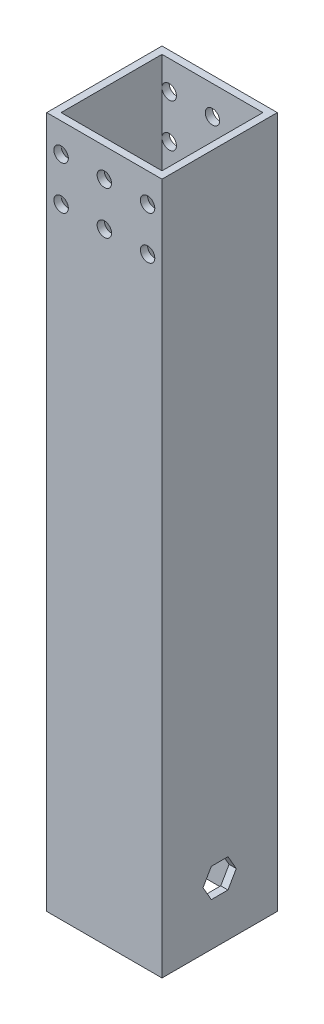
SolidWorks part; units mm, degrees
ref_plane "Front Plane" through (0, 0, 0) normal (0, 0, 1) x (1, 0, 0)
ref_plane "Top Plane" through (0, 0, 0) normal (0, 1, 0) x (1, 0, 0)
ref_plane "Right Plane" through (0, 0, 0) normal (1, 0, 0) x (0, 0, -1)
sketch "Sketch1" plane through (0, 0, 0) normal (0, 1, 0) x (1, 0, 0)
  line L1 (-25.4, -25.4) -> (25.4, -25.4)
  line L2 (-25.4, -25.4) -> (-25.4, 25.4)
  line L3 (-25.4, 25.4) -> (25.4, 25.4)
  line L4 (25.4, -25.4) -> (25.4, 25.4)
  line L5 (-25.4, -25.4) -> (25.4, 25.4) construction
  line L6 (-25.4, 25.4) -> (25.4, -25.4) construction
  line L7 (-22.225, -22.225) -> (22.225, -22.225)
  line L8 (-22.225, -22.225) -> (-22.225, 22.225)
  line L9 (-22.225, 22.225) -> (22.225, 22.225)
  line L10 (22.225, -22.225) -> (22.225, 22.225)
  line L11 (-22.225, -22.225) -> (22.225, 22.225) construction
  line L12 (-22.225, 22.225) -> (22.225, -22.225) construction
  point P0 (0, 0)
  point P6 (0, 0)
  dimension "D1" = 50.8
  dimension "D2" = 50.8
  dimension "D3" = 3.175
extrude "Boss-Extrude1" add sketch "Sketch1" along normal blind 304.8
sketch "Sketch2" plane through (0, 0, 25.4) normal (0, 0, 1) x (1, 0, 0)
  line L0 (-25.4, 304.8) -> (-25.4, 0) construction
  line L1 (-25.4, 304.8) -> (25.4, 304.8) construction
  circle A0 centre (-19.05, 292.1) radius 3.175
  point P4 (0, 0)
  dimension "D1" = 6.35
  dimension "D2" = 6.35
  dimension "D3" = 12.7
extrude "Cut-Extrude1" cut sketch "Sketch2" against normal blind 101.6
pattern_linear "LPattern1" count 3 spacing 19.05 along (1, 0, 0) count 2 spacing 19.05 along (0, -1, 0) of "Cut-Extrude1"
sketch "Sketch3" plane through (25.4, 0, 0) normal (1, 0, 0) x (0, 0, -1)
  line L0 (-25.4, 0) -> (25.4, 0) construction
  line L1 (-3.6662, 19.05) -> (3.6662, 19.05)
  line L2 (3.6662, 19.05) -> (7.3323, 25.4)
  line L3 (7.3323, 25.4) -> (3.6662, 31.75)
  line L4 (3.6662, 31.75) -> (-3.6662, 31.75)
  line L5 (-3.6662, 31.75) -> (-7.3323, 25.4)
  line L6 (-7.3323, 25.4) -> (-3.6662, 19.05)
  line L7 (25.4, 304.8) -> (25.4, 0) construction
  circle A0 centre (0, 25.4) radius 6.35 construction
  point P14 (1.231, 5.4135)
  dimension "D1" = 12.7
  dimension "D2" = 0
  dimension "D3" = 25.4
  dimension "D4" = 25.4
extrude "Cut-Extrude2" cut sketch "Sketch3" against normal through all
